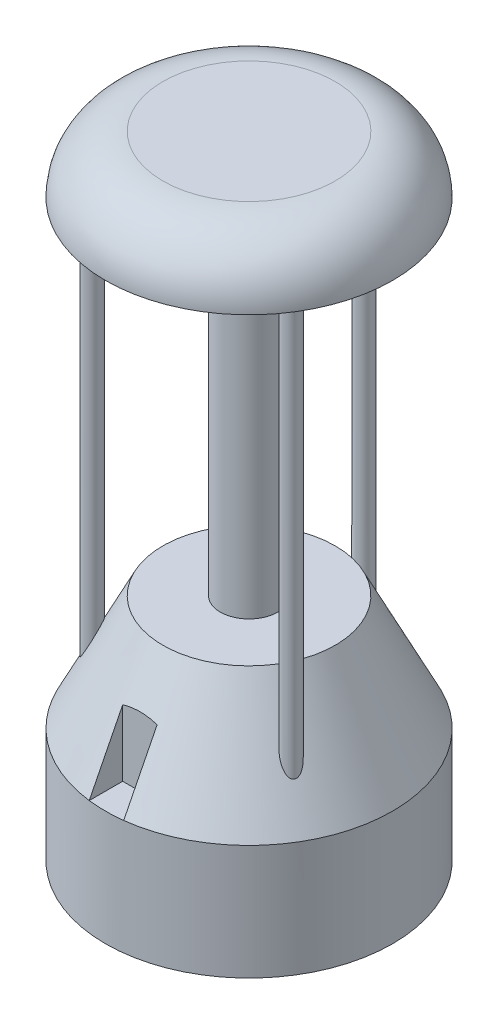
SolidWorks part; units mm, degrees
ref_plane "Front Plane" through (0, 0, 0) normal (0, 0, 1) x (1, 0, 0)
ref_plane "Top Plane" through (0, 0, 0) normal (0, 1, 0) x (1, 0, 0)
ref_plane "Right Plane" through (0, 0, 0) normal (1, 0, 0) x (0, 0, -1)
sketch "Sketch1" plane through (0, 0, 0) normal (0, 1, 0) x (1, 0, 0)
  circle A0 centre (0, 0) radius 25
  dimension "D1" = 50
extrude "Bottom-cylinder" add sketch "Sketch1" along normal blind 20 contours A0
sketch "Sketch2" plane through (0, 20, 0) normal (0, 1, 0) x (1, 0, 0)
  circle A0 centre (0, 0) radius 25
  circle A1 centre (0, 0) radius 25 construction
  dimension "D1" = 50
ref_plane "Plane1" through (0, 40, 0) normal (0, -1, 0) x (-1, 0, 0)
sketch "Sketch3" plane through (0, 40, 0) normal (0, -1, 0) x (-1, 0, 0)
  circle A0 centre (0, 0) radius 15
  dimension "D1" = 30
loft "Cone-top" add profiles "Sketch3", "Sketch2" connector at (-5.9053, 40, 13.7887) connector at (-9.0422, 20, 23.3075)
ref_plane "Plane2" through (0, 20, 0) normal (0, 1, 0) x (1, 0, 0)
sketch "Sketch5" plane through (0, 20, 0) normal (0, 1, 0) x (1, 0, 0)
  circle A0 centre (0, 20) radius 1.5
  circle A1 centre (17.3205, -10) radius 1.5
  circle A2 centre (-17.3205, -10) radius 1.5
  point P10 (0, 0)
  dimension "D1" = 3
  dimension "D2" = 3
  dimension "D3" = 17.3205
extrude "UVC-rods" add sketch "Sketch5" along normal blind 80
ref_plane "Plane3" through (0, 100, 0) normal (0, 1, 0) x (1, 0, 0)
sketch "Sketch6" plane through (0, 100, 0) normal (0, 1, 0) x (1, 0, 0)
  circle A0 centre (0, 0) radius 25
  dimension "D1" = 50
extrude "Top" add sketch "Sketch6" along normal blind 10 contours A0
fillet "Fillet1" radius 10 1 edges at (0, 110, 25)
sketch "Sketch8" plane through (0, 20, 0) normal (0, 1, 0) x (1, 0, 0)
  line L0 (-3, -25) -> (-3, -19)
  line L1 (-3, -25) -> (3, -25)
  line L3 (-3, -19) -> (3, -19)
  line L4 (3, -25) -> (3, -19)
  dimension "D1" = 3
  dimension "D2" = 6
  dimension "D3" = 19
extrude "Lidar-cubby" cut sketch "Sketch8" along normal up to next
sketch "Sketch9" plane through (0, 40, 0) normal (0, 1, 0) x (1, 0, 0)
  circle A0 centre (0, 0) radius 5
  circle A1 centre (0, 0) radius 15 construction
  dimension "D1" = 10
extrude "Boss-Extrude1" add sketch "Sketch9" along normal up to next
